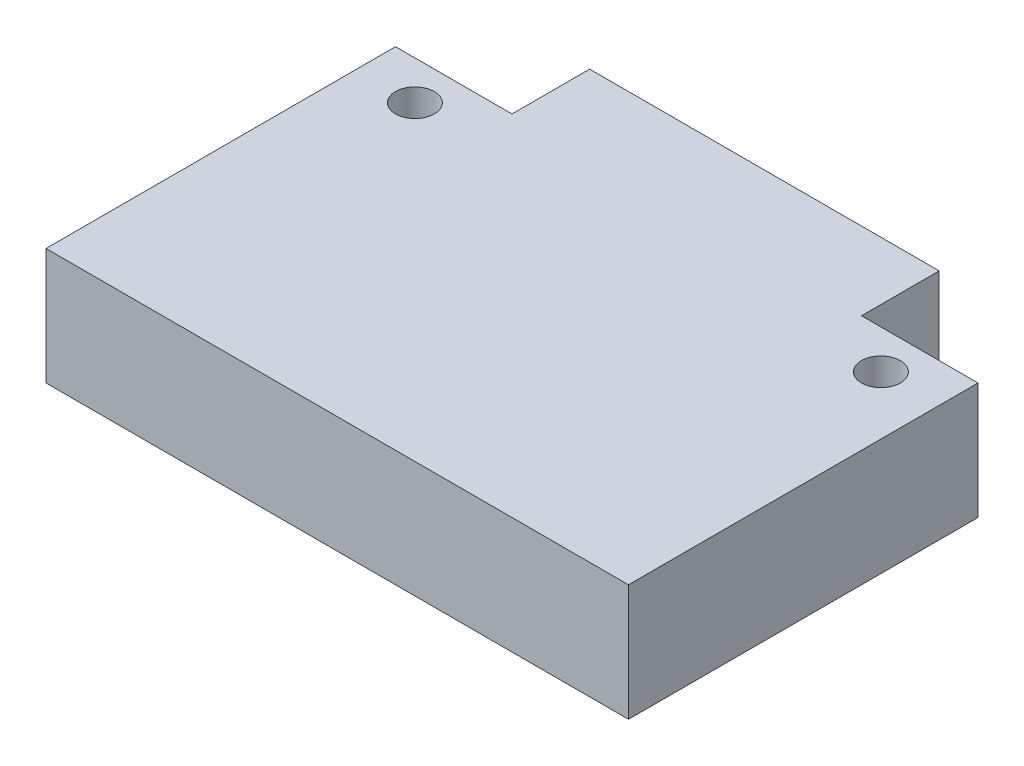
SolidWorks part; units mm, degrees
ref_plane "Front Plane" through (0, 0, 0) normal (0, 0, 1) x (1, 0, 0)
ref_plane "Top Plane" through (0, 0, 0) normal (0, 1, 0) x (1, 0, 0)
ref_plane "Right Plane" through (0, 0, 0) normal (1, 0, 0) x (0, 0, -1)
sketch "Sketch1" plane through (0, 0, 0) normal (0, 1, 0) x (1, 0, 0)
  line L0 (0, 18) -> (6, 18)
  line L1 (0, 0) -> (30, 0)
  line L2 (0, 0) -> (0, 18)
  line L3 (6, 22) -> (24, 22)
  line L4 (30, 0) -> (30, 18)
  line L5 (6, 18) -> (6, 22)
  line L6 (24, 22) -> (24, 18)
  line L7 (24, 18) -> (30, 18)
  dimension "D1" = 6
  dimension "D2" = 6
  dimension "D3" = 30
  dimension "D4" = 22
  dimension "D5" = 4
extrude "Boss-Extrude1" add sketch "Sketch1" along normal blind 6
sketch "Sketch2" plane through (0, 6, 0) normal (0, 1, 0) x (1, 0, 0)
  line L0 (6, 18) -> (0, 18) construction
  line L1 (0, 18) -> (0, 0) construction
  line L2 (30, 0) -> (30, 18) construction
  circle A0 centre (3, 16) radius 1
  circle A1 centre (27, 16) radius 1
  dimension "D1" = 2
  dimension "D2" = 2
  dimension "D3" = 3
  dimension "D4" = 3
extrude "Cut-Extrude1" cut sketch "Sketch2" against normal through all
